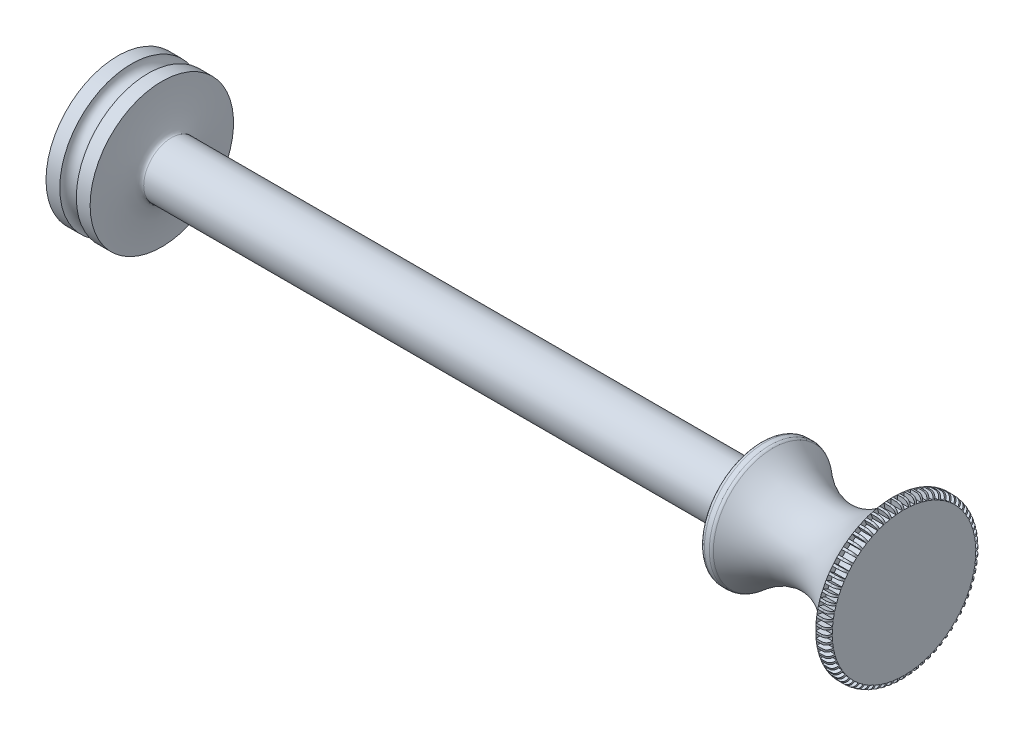
SolidWorks part; units mm, degrees
material "Mosaz"
ref_plane "Přední rovina" through (0, 0, 0) normal (0, 0, 1) x (1, 0, 0)
ref_plane "Horní rovina" through (0, 0, 0) normal (0, 1, 0) x (1, 0, 0)
ref_plane "Pravá rovina" through (0, 0, 0) normal (1, 0, 0) x (0, 0, -1)
sketch "Skica1" plane through (0, 0, 0) normal (0, 1, 0) x (1, 0, 0)
  line L0 (0, 0) -> (-8.4197, 0)
  line L1 (0, 0) -> (45, 0)
  line L2 (-13.2791, 4) -> (-12.0291, 4)
  line L3 (-14.1385, -2.5) -> (25.1376, -2.5)
  line L4 (-10.5291, 4) -> (-9.2791, 4)
  line L5 (45, 0) -> (45, 3)
  line L6 (45, 3) -> (46, 3)
  line L7 (-11.2791, 4.7272) -> (-11.2791, -0.3702) construction
  line L8 (25.1376, -2.5) -> (58, -2.5)
  line L9 (-14.1385, -2.5) -> (-14.1385, 0)
  line L10 (57, 4.5) -> (58, 4.5)
  line L11 (58, 4.5) -> (58, -2.5)
  arc A0 (-12.0291, 4) -> (-10.5291, 4) centre (-11.2791, 4) ccw
  ellipse E0 centre (-14.0079, 3.9761) end of major axis (-14.1385, 0) minor radius 0.7277 (-14.1385, 0) -> (-13.2791, 4) ccw
  ellipse E1 centre (-8.5503, 3.9761) end of major axis (-8.4197, 0) minor radius 0.7277 (-8.4197, 0) -> (-9.2791, 4) cw
  spline S0 degree 2 poles (46, 3) (51.8258, -2.2777) (57, 4.5) knots 0 0 0 1 1 1
  dimension "D9" = 1.5
  dimension "D2" = 45
  dimension "D3" = 2.5
  dimension "D4" = 3
  dimension "D5" = 1
  dimension "D6" = 7
  dimension "D7" = 4
  dimension "D8" = 1
  dimension "D10" = 11
  dimension "D11" = 6.5
  dimension "D13" = 59.1385
  dimension "D14" = 4
revolve "Rotovat1" add sketch "Skica1" angle 360 about L3
fillet "Zaoblit2" radius 0.5 1 edges at (58, 0, 9.5)
fillet "Zaoblit3" radius 0.4 2 edges at (45, 0, 8) (46, 0, 8)
ref_plane "Rovina1" through (0, 0, 9.5) normal (0, 0, 1) x (1, 0, 0)
sketch "Skica2" plane through (0, 0, 9.5) normal (0, 0, 1) x (1, 0, 0)
  line L0 (57, 0) -> (57, 0.4)
  line L1 (57, 0) -> (59, 0)
  line L2 (59, 0) -> (59, 0.4)
  line L3 (57, 0.4) -> (59, 0.4)
  line L4 (58, 0) -> (72.8698, 0) construction
  line L5 (58, -6.5) -> (58, 6.5) construction
  dimension "D1" = 2
  dimension "D2" = 0.4
extrude "Odebrat vysunutím1" cut sketch "Skica2" against normal blind 0.5
ref_axis "Osa1" through (45, 0, 2.5) along (-1, 0, 0)
pattern_circular "Kruhové pole1" count 72 every 5 about axis through (45, 0, 2.5) along (-1, 0, 0) of "Odebrat vysunutím1"
